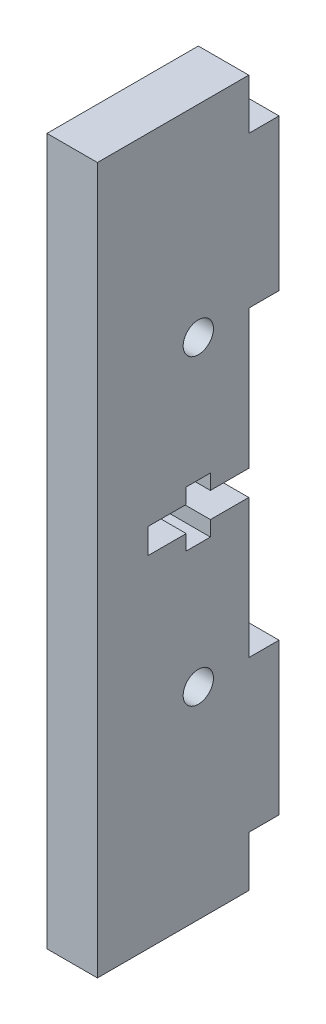
SolidWorks part; units mm, degrees
material "PMMA"
ref_plane "Front Plane" through (0, 0, 0) normal (0, 0, 1) x (1, 0, 0)
ref_plane "Top Plane" through (0, 0, 0) normal (0, 1, 0) x (1, 0, 0)
ref_plane "Right Plane" through (0, 0, 0) normal (1, 0, 0) x (0, 0, -1)
sketch "Schizzo1" plane through (0, 0, 0) normal (1, 0, 0) x (0, 0, -1)
  line L0 (-7.5, 35) -> (7.5, -35) construction
  line L1 (-7.5, 35) -> (7.5, 35)
  line L2 (-7.5, 35) -> (-7.5, -35)
  line L3 (-7.5, -35) -> (7.5, -35)
  line L4 (7.5, 35) -> (7.5, -35)
  point P4 (0, 0)
  dimension "D1" = 70
  dimension "D2" = 15
extrude "Estrusione-Estrusione1" add sketch "Schizzo1" along normal blind 5
sketch "Schizzo2" plane through (0, 0, -7.5) normal (0, 0, -1) x (-1, 0, 0)
  line L0 (-5, 0) -> (0, 0) construction
  line L1 (-5, 30) -> (0, 30)
  line L2 (-5, 30) -> (-5, 15)
  line L3 (-5, 15) -> (0, 15)
  line L4 (0, 30) -> (0, 15)
  line L5 (-5, -35) -> (-5, 35) construction
  line L7 (0, -35) -> (0, 35) construction
  line L8 (-5, -30) -> (-5, -15)
  line L9 (-5, -15) -> (0, -15)
  line L10 (0, -30) -> (0, -15)
  line L11 (-5, -30) -> (0, -30)
  dimension "D1" = 15
  dimension "D2" = 15
extrude "Estrusione-Estrusione2" add sketch "Schizzo2" along normal blind 3
sketch "Schizzo4" plane through (0, 0, 0) normal (1, 0, 0) x (0, 0, -1)
  line L0 (2.5, 35) -> (2.5, -35) construction
  line L1 (7.5, 35) -> (-7.5, 35) construction
  line L2 (-7.5, -35) -> (7.5, -35) construction
  line L3 (7.5, 30) -> (7.5, 35) construction
  line L4 (7.5, 0) -> (-7.5, 0) construction
  line L5 (7.5, -15) -> (7.5, 15) construction
  line L6 (-7.5, 35) -> (-7.5, -35) construction
  line L7 (7.5, 30) -> (7.5, 35) construction
  line L8 (10.5, 15) -> (-7.5, 15) construction
  line L9 (8.9133, 0) -> (18.9133, 0) construction
  line L10 (-2.5, 1.25) -> (1.3, 1.25)
  line L11 (1.3, 1.25) -> (1.3, 2.75)
  line L12 (1.3, 2.75) -> (3.7, 2.75)
  line L13 (3.7, 2.75) -> (3.7, 1.25)
  line L14 (3.7, 1.25) -> (7.5, 1.25)
  line L15 (7.5, 1.25) -> (7.5, -1.25)
  line L16 (7.5, -1.25) -> (3.7, -1.25)
  line L17 (3.7, -1.25) -> (3.7, -2.75)
  line L18 (3.7, -2.75) -> (1.3, -2.75)
  line L19 (1.3, -2.75) -> (1.3, -1.25)
  line L20 (1.3, -1.25) -> (-2.5, -1.25)
  line L21 (-2.5, -1.25) -> (-2.5, 1.25)
  line L22 (24.8004, 0) -> (9.8004, 0) construction
  circle A1 centre (2.5, 15) radius 1.5
  circle A2 centre (2.5, -15) radius 1.5
  dimension "D2" = 3
  dimension "D3" = 20
  dimension "D1" = 5
  dimension "D4" = 5.5
  dimension "D5" = 2.5
  dimension "D6" = 1.25
  dimension "D7" = 2.75
  dimension "D8" = 2.4
  dimension "D9" = 10
extrude "Taglio-Estrusione2" cut sketch "Schizzo4" along direction (1, 0, 0) on the side of the normal through all
equation "\"Thickness5\"=5"
equation "\"D1@Estrusione-Estrusione1\"=\"Thickness5\""
equation "\"Thickness3\"=3"
equation "\"D1@Estrusione-Estrusione2\"=\"Thickness3\""
